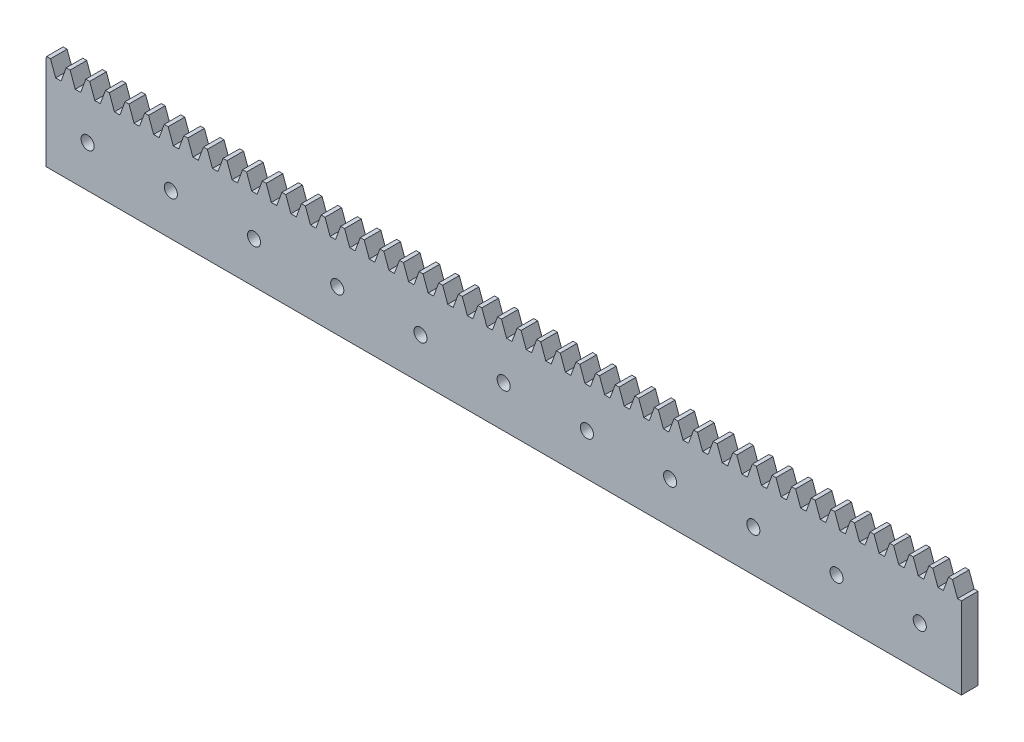
SolidWorks part; units mm, degrees
extrude "Blank" add sketch "BlankSke" against normal blind 4
sketch "BlankSke" plane through (0, 0, 0) normal (0, 0, 1) x (1, 0, 0)
  line L1 (0, 0) -> (660, 0)
  line L2 (0, 0) -> (0, 23)
  line L3 (0, 23) -> (660, 23)
  line L4 (660, 0) -> (660, 23)
  dimension "Length" = 660
ref_plane "Plane1" through (0, 0, 0) normal (0, 0, 1) x (1, 0, 0)
ref_plane "Plane2" through (0, 0, 0) normal (0, 1, 0) x (1, 0, 0)
ref_plane "Plane3" through (0, 0, 0) normal (1, 0, 0) x (0, 0, -1)
other "Configuration Table"
sketch "HoldingSke" plane through (0, 0, 0) normal (0, 1, 0) x (1, 0, 0)
  line L0 (0, 0) -> (0.0928, 0.6602)
  line L1 (-15, 0) -> (100, 0) construction
  line L2 (0, 0) -> (-2.1039, 2.3779)
  line L3 (0, 0) -> (-11.863, 4.5341)
  line L4 (0, 0) -> (-6.8053, 5.3169)
  line L5 (0, 0) -> (-23.7986, -8.8762)
  line L6 (0, 0) -> (-10.5278, -7.1032)
  line L9 (-71.009, 38.7566) -> (549.1882, 264.4899)
  line L10 (-76.2, 3.8779) -> (-54.7, 3.8779)
  line L11 (0, 0) -> (-4, 0)
  line L12 (-76.2, 101.6) -> (-76.147, 101.6)
  line L13 (24.9733, 27.94) -> (52.9518, 28.4284)
  line L14 (24.9733, 27.94) -> (24.9743, 27.94)
  line L15 (24.9733, 27.94) -> (100.4006, 29.5858)
  circle A0 centre (0, 0) radius 19.05
  circle A1 centre (0, 0) radius 10.75
  circle A2 centre (0, 0) radius 12.7
  dimension "Num_teeth" = 142
  dimension "Width" = 4
  dimension "Length" = 660
  dimension "Pitch_height" = 21.5
sketch "TooCutSkeIll" plane through (0, 0, 0) normal (0, 0, 1) x (1, 0, 0)
  line L0 (-1.8687, 22.9605) -> (-0.7447, 19.8724)
  line L1 (-0.3914, 19.625) -> (0.3914, 19.625)
  line L2 (0.7447, 19.8724) -> (1.8687, 22.9605)
  line L3 (660, 23) -> (0, 23) construction
  line L4 (0, 0) -> (0, 64.897) construction
  line L5 (-13.208, 21.5) -> (12.954, 21.5) construction
  line L6 (0, 0) -> (660, 0) construction
  line L7 (1.3371, 21.5) -> (1.3371, 48.7463) construction
  line L8 (-1.3371, 21.5) -> (-1.3371, 48.7463) construction
  line L9 (1.9251, 23) -> (1.9251, 23.0254)
  line L10 (-1.9251, 23) -> (-1.9251, 23.0254)
  line L11 (-1.9251, 23.0254) -> (1.9251, 23.0254)
  arc A0 (0.3914, 19.625) -> (0.7447, 19.8724) centre (0.3914, 20.001) ccw
  arc A1 (-0.7447, 19.8724) -> (-0.3914, 19.625) centre (-0.3914, 20.001) ccw
  arc A2 (1.9251, 23) -> (1.8687, 22.9605) centre (1.9251, 22.94) ccw
  arc A3 (-1.8687, 22.9605) -> (-1.9251, 23) centre (-1.9251, 22.94) ccw
  dimension "Addendum_plus" = 1.5254
  dimension "Pitch_height" = 21.5
  dimension "Pressure_angle" = 20
  dimension "Gap_width" = 2.6742
  dimension "Dedendum" = 1.875
extrude "ToothCutIll" [suppressed] cut sketch "TooCutSkeIll" against normal through all
sketch "TooCutSkeSim" plane through (0, 0, 0) normal (0, 0, 1) x (1, 0, 0)
  line L0 (0.6547, 19.625) -> (-0.6547, 19.625)
  line L1 (1.8923, 23.0254) -> (0.6547, 19.625)
  line L2 (0, 17.4625) -> (0, 53.467) construction
  line L3 (1.8923, 23.0254) -> (-1.8923, 23.0254)
  line L6 (-1.8923, 23.0254) -> (-0.6547, 19.625)
  line L9 (-1.3371, 21.5) -> (1.3371, 21.5) construction
  line L10 (0, 0) -> (660, 0) construction
  line L11 (1.3371, 21.5) -> (1.3371, 53.467) construction
  line L12 (-1.3371, 21.5) -> (-1.3371, 53.467) construction
  dimension "Addendum_plus" = 1.5254
  dimension "Pitch_height" = 21.5
  dimension "Pressure_angle" = 20
  dimension "Gap_width" = 2.6742
  dimension "Dedendum" = 1.875
extrude "ToothCutSim" cut sketch "TooCutSkeSim" against normal through all
pattern_linear "TeethCuts" count 141 spacing 4.7124 along (1, 0, 0) of "ToothCutSim"
sketch "草图2" plane through (0, 0, 0) normal (0, 0, 1) x (1, 0, 0)
  line L0 (660, 0) -> (660, 19.625) construction
  line L2 (0, 0) -> (660, 0) construction
  circle A0 centre (650, 10) radius 1.575
  circle A1 centre (630, 10) radius 1.575
  circle A2 centre (610, 10) radius 1.575
  circle A3 centre (590, 10) radius 1.575
  circle A4 centre (570, 10) radius 1.575
  circle A5 centre (550, 10) radius 1.575
  circle A6 centre (530, 10) radius 1.575
  circle A7 centre (510, 10) radius 1.575
  circle A8 centre (490, 10) radius 1.575
  circle A9 centre (470, 10) radius 1.575
  circle A10 centre (450, 10) radius 1.575
  circle A11 centre (430, 10) radius 1.575
  circle A12 centre (410, 10) radius 1.575
  circle A13 centre (390, 10) radius 1.575
  circle A14 centre (370, 10) radius 1.575
  circle A15 centre (350, 10) radius 1.575
  circle A16 centre (330, 10) radius 1.575
  circle A17 centre (310, 10) radius 1.575
  circle A18 centre (290, 10) radius 1.575
  circle A19 centre (270, 10) radius 1.575
  circle A20 centre (250, 10) radius 1.575
  circle A21 centre (230, 10) radius 1.575
  circle A22 centre (210, 10) radius 1.575
  circle A23 centre (190, 10) radius 1.575
  circle A24 centre (170, 10) radius 1.575
  circle A25 centre (150, 10) radius 1.575
  circle A26 centre (130, 10) radius 1.575
  circle A27 centre (110, 10) radius 1.575
  circle A28 centre (90, 10) radius 1.575
  circle A29 centre (70, 10) radius 1.575
  circle A30 centre (50, 10) radius 1.575
  circle A31 centre (30, 10) radius 1.575
  circle A32 centre (10, 10) radius 1.575
  dimension "D4" = 3.15
  dimension "D1" = 10
  dimension "D3" = 20
  dimension "D5" = 10
  dimension "D2" = 33
extrude "切除-拉伸2" cut sketch "草图2" against normal through all
sketch "草图3" plane through (0, 0, 0) normal (0, 0, 1) x (1, 0, 0)
  line L1 (0, 0) -> (440, 0)
  line L2 (0, 0) -> (0, 84.8236)
  line L3 (0, 84.8236) -> (440, 84.8236)
  line L4 (440, 0) -> (440, 84.8236)
  dimension "D1" = 440
extrude "切除-拉伸3" cut sketch "草图3" against normal through all
equation "' \"Module@HoldingSke\" = 6.35"
equation "' \"Num_teeth@HoldingSke\" = 12"
equation "' \"Ap@HoldingSke\" =  20"
equation "' \"Ap@HoldingSke\" = 20"
equation "' \"Width@HoldingSke\" = 0.25 * 25.4"
equation "' \"Show_teeth@HoldingSke\" = 500"
equation "' \"Backlash@HoldingSke\" = 0.009 * 25.4"
equation "' \"Addendum_fac@HoldingSke\" = 1.0"
equation "' \"Dedendum_fac@HoldingSke\" = 1.25"
equation "' \"Dedendum_add@HoldingSke\" = 0.00005 * 25.4"
equation "' \"Clearance_fac@HoldingSke\" = 0.25"
equation "' \"Pitch_height@HoldingSke\" = 1 * 25.4"
equation "' \"Length@HoldingSke\" = 4.71 * 25.4"
equation "\"Pitch@HoldingSke\" = 1 / \"Module@HoldingSke\""
equation "\"MPH@HoldingSke\" = \"Dedendum_fac@HoldingSke\" / \"Pitch@HoldingSke\" + 2 * \"Dedendum_add@HoldingSke\" + 0.002 * 25.4"
equation "\"MPH@HoldingSke\" = ((sgn( \"MPH@HoldingSke\" - \"Pitch_height@HoldingSke\")+1)*( \"MPH@HoldingSke\" - \"Pitch_height@HoldingSke\"))/2 + \"Pitch_height@HoldingSke\""
equation "\"Blank_height@BlankSke\" = \"Pitch_height@HoldingSke\" + \"Addendum_fac@HoldingSke\"  / \"Pitch@HoldingSke\" "
equation "\"Length@BlankSke\" =  \"Length@HoldingSke\""
equation "\"Face_width@Blank\" = \"Width@HoldingSke\""
equation "\"Pressure_angle@TooCutSkeIll\" = \"Ap@HoldingSke\""
equation "\"Addendum_plus@TooCutSkeIll\" =  \"Addendum_fac@HoldingSke\"  / \"Pitch@HoldingSke\" + 0.001 *25.4"
equation "\"Dedendum@TooCutSkeIll\" = \"Dedendum_fac@HoldingSke\"  / \"Pitch@HoldingSke\""
equation "\"Pitch_height@TooCutSkeIll\" =  \"MPH@HoldingSke\""
equation "\"Gap_width@TooCutSkeIll\" = 3.14159265 / 2 / \"Pitch@HoldingSke\" + 6 * \"Backlash@HoldingSke\""
equation "\"Pressure_angle@TooCutSkeSim\" = \"Ap@HoldingSke\""
equation "\"Addendum_plus@TooCutSkeSim\" =  \"Addendum_fac@HoldingSke\"  / \"Pitch@HoldingSke\" + 0.001 * 25.4"
equation "\"Dedendum@TooCutSkeSim\" = \"Dedendum_fac@HoldingSke\"  / \"Pitch@HoldingSke\""
equation "\"Pitch_height@TooCutSkeSim\" =  \"MPH@HoldingSke\""
equation "\"Gap_width@TooCutSkeSim\" = 3.14159265 / 2 / \"Pitch@HoldingSke\" + 6 * \"Backlash@HoldingSke\""
equation "\"Root_fillet@TooCutSkeIll\" = \"Clearance_fac@HoldingSke\" / \"Pitch@HoldingSke\" + \"Dedendum_add@HoldingSke\""
equation "\"Break_rad@TooCutSkeIll\" = 0.02 / \"Pitch@HoldingSke\" * 2"
equation "\"Linear_pitch@TeethCuts\" = 3.14159265 / \"Pitch@HoldingSke\""
equation "\"Num_teeth@HoldingSke\" = int( ( \"Length@HoldingSke\" + 0 ) / (3.14159265 / \"Pitch@HoldingSke\")) + 0.9999  + 1"
equation " \"Num_teeth@TeethCuts\" = int( \"Show_teeth@HoldingSke\" ) + 1"
equation " \"Num_teeth@TeethCuts\" = ((sgn( \"Num_teeth@TeethCuts\" - \"Num_teeth@HoldingSke\" )-1)*( \"Num_teeth@TeethCuts\" - \"Num_teeth@HoldingSke\" ))/-2+ \"Num_teeth@HoldingSke\""
equation " \"Num_teeth@TeethCuts\" = ((sgn( \"Num_teeth@TeethCuts\" - 2.0)+1)*( \"Num_teeth@TeethCuts\" - 2.0))/2 +2.0"
